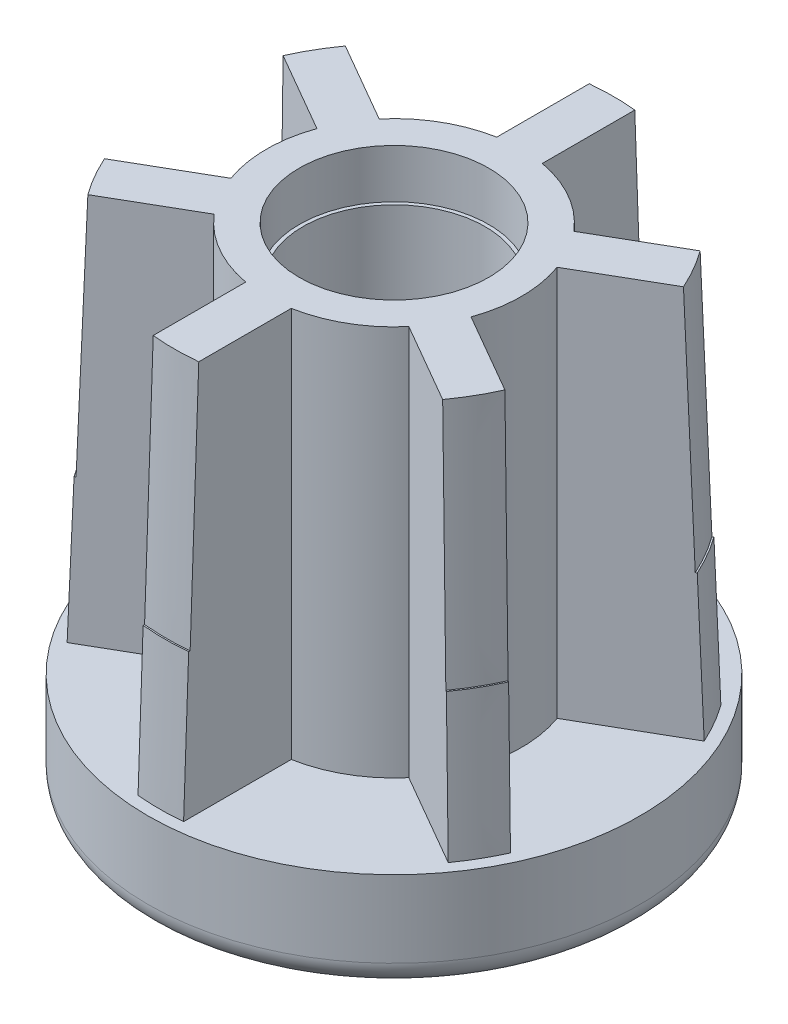
SolidWorks part; units mm, degrees
ref_plane "Front Plane" through (0, 0, 0) normal (0, 0, 1) x (1, 0, 0)
ref_plane "Top Plane" through (0, 0, 0) normal (0, 1, 0) x (1, 0, 0)
ref_plane "Right Plane" through (0, 0, 0) normal (1, 0, 0) x (0, 0, -1)
sketch "Sketch1" plane through (0, 0, 0) normal (1, 0, 0) x (0, 0, -1)
  line L0 (0, 21.4312) -> (0, -21.4312) construction
  line L1 (0, -21.4312) -> (21.4313, -21.4313)
  line L2 (21.4313, -21.4313) -> (21.4313, -12.6048)
  line L3 (21.4313, -12.6048) -> (0, -12.6048)
  line L4 (7.9375, -21.4313) -> (7.9375, 0.7937)
  line L5 (7.9375, 0.7937) -> (0, 0.7937)
  line L6 (9.525, -21.4313) -> (9.525, 0.7937)
  line L7 (9.525, 0.7937) -> (7.9375, 0.7937)
  line L8 (11.1125, -12.6048) -> (11.1125, 21.4312)
  line L9 (11.1125, 21.4312) -> (0, 21.4312)
  line L10 (19.8438, -12.6048) -> (19.8438, 21.4313)
  line L11 (19.8438, 21.4313) -> (11.1125, 21.4312)
  line L12 (19.8438, -12.6048) -> (19.2496, 21.4313)
  line L13 (9.525, 0.7937) -> (11.1125, 0.7937) construction
  line L14 (8.1875, -21.2869) -> (6.1877, -22.4415) construction
  line L15 (6.1877, -22.4415) -> (8.1875, -23.596) construction
  line L16 (8.1875, -23.596) -> (8.1875, -21.2869) construction
  line L17 (8.0625, -21.3591) -> (8.0625, -23.5239)
  line L18 (8.0625, -23.5239) -> (6.4377, -22.5858)
  line L19 (6.4377, -22.5858) -> (6.4377, -22.2972)
  line L20 (6.4377, -22.2972) -> (8.0625, -21.3591)
  line L21 (6.4377, -22.4415) -> (6.1877, -22.4415) construction
  line L22 (7.9375, -21.4313) -> (7.9375, -23.4517) construction
  line L23 (8.1875, -22.4415) -> (7.9375, -22.4415) construction
  line L24 (-7.9375, -21.4313) -> (-7.9375, 0.7937)
  point P2 (0, 0)
  point P16 (10.3188, 0.7937)
  point P31 (8.0625, -22.4415)
  point P33 (19.8438, -12.6048)
  point P35 (-7.9375, -10.3188)
  point P36 (7.9375, -21.4313)
  point P37 (7.9375, -10.3188)
  dimension "Base Diameter" = 42.8625
  dimension "Thread Diameter" = 15.875
  dimension "Thread Depth" = 22.225
  dimension "D1" = 19.05
  dimension "D4" = 22.225
  dimension "Insert Depth" = 34.036
  dimension "Overall Height" = 42.8625
  dimension "For Leg ID" = 39.6875
  dimension "D2" = 1
  dimension "Pitch" = 2.3091
  dimension "D5" = 0.2886
sketch "Sketch2" plane through (0, 0, 0) normal (0, 1, 0) x (1, 0, 0)
  line L0 (-1.9844, 19.7443) -> (1.9844, 19.7443)
  line L1 (-1.9844, 19.7443) -> (-1.9844, 10.9339)
  line L2 (-1.9844, 10.9339) -> (1.9844, 10.9339)
  line L3 (1.9844, 10.9339) -> (1.9844, 19.7443)
  circle A0 centre (0, 0) radius 19.8438
  circle A1 centre (0, 0) radius 11.1125
  dimension "D1" = 3.9688
sketch "Sketch8" plane through (0, 0, 0) normal (1, 0, 0) x (0, 0, -1)
  line L0 (11.1125, -12.6048) -> (11.1125, 21.4312)
  line L1 (11.1125, 21.4312) -> (7.9375, 21.4312)
  line L2 (11.1125, 21.4312) -> (0, 21.4312) construction
  line L3 (7.9375, 21.4312) -> (7.9375, 0.7937)
  line L4 (7.9375, 0.7937) -> (9.525, 0.7937)
  line L9 (0, 21.4312) -> (0, -12.6048) construction
  line L10 (9.525, 0.7937) -> (9.525, -21.4313)
  line L11 (9.525, -21.4313) -> (21.4313, -21.4313)
  line L12 (21.4313, -21.4313) -> (21.4313, -12.6048)
  line L13 (21.4313, -12.6048) -> (11.1125, -12.6048)
revolve "Revolve2" add sketch "Sketch8" angle 360 about L9
sketch "Sketch9" plane through (-13.335, -12.6047, 0) normal (0, 1, 0) x (0, 0, -1)
  line L4 (10.9339, -11.3506) -> (10.9339, -15.3194)
  line L7 (10.9339, -11.3506) -> (21.3392, -11.3506)
  line L8 (10.9339, -15.3194) -> (21.3392, -15.3194)
  circle A0 centre (0, -13.335) radius 21.4313 construction
  arc A1 (21.3392, -15.3194) -> (21.3392, -11.3506) centre (0, -13.335) ccw
extrude "Boss-Extrude3" add sketch "Sketch9" along normal up to vertex (34.036 mm away) up to point (0, 21.4312, 0)
pattern_circular "CirPattern2" count 6 over 360 about axis through (0, -21.4312, 0) along (0, 1, 0) of "Boss-Extrude3"
sketch "Sketch15" plane through (0, 0, 0) normal (1, 0, 0) x (0, 0, -1)
  line L0 (19.8438, -12.6048) -> (21.4313, -12.6048) construction
  line L1 (20.411, -12.6048) -> (19.9708, 0)
  line L2 (19.9708, 0) -> (19.8438, 0)
  line L3 (7.9375, 21.4312) -> (-7.9375, 21.4312) construction
  line L4 (19.8438, 0) -> (19.0954, 21.4312)
  line L5 (19.0954, 21.4312) -> (21.4313, 21.4312)
  line L6 (21.4313, 21.4312) -> (21.4313, -12.6048)
  line L7 (21.4313, -12.6048) -> (20.411, -12.6048)
  line L8 (7.9375, 21.4312) -> (8.255, 21.4312)
  line L9 (7.9375, 21.4312) -> (7.9375, 17.1767)
  line L10 (7.9375, 17.1767) -> (8.255, 17.1767)
  line L11 (8.255, 21.4312) -> (8.255, 17.1767)
  dimension "D1" = 2
  dimension "D2" = 0.127
  dimension "D3" = 0.3175
  dimension "D4" = 4.2545
revolve "Cut-Revolve1" cut sketch "Sketch15" angle 360 about L0
sketch "Sketch10" plane through (0, 0, 0) normal (1, 0, 0) x (0, 0, -1)
  line L0 (0, 0.7937) -> (0, -21.4312) construction
  line L2 (9.525, 0.7937) -> (7.9375, 0.7937)
  line L3 (9.525, 0.7937) -> (9.525, -21.4313)
  line L4 (9.525, -21.4313) -> (7.9375, -21.4313)
  line L5 (7.9375, 0.7937) -> (7.9375, -21.4313)
revolve "Revolve3" add sketch "Sketch10" angle 360 about L0
sketch "Sketch11" plane through (0, -21.4313, 0) normal (0, -1, 0) x (1, 0, 0)
  circle A0 centre (0, 0) radius 7.9375 construction
  circle A1 centre (0, 0) radius 7.9375
fillet "Fillet2" radius 2.1431 1 edges at (0, -21.4312, 21.4312)
curve "Helix/Spiral1" pitch 2.3091 height 24.5341 radius 7.9375 centre (0, -21.4313, 0) axis (0, 1, 0) start towards (0, 0, -1)
sketch "Sketch12" plane through (0, 0, 0) normal (1, 0, 0) x (0, 0, -1)
  line L0 (8.0625, -21.3591) -> (8.0625, -23.5239) construction
  line L1 (6.4377, -22.2972) -> (8.0625, -21.3591) construction
  line L2 (6.4377, -22.5858) -> (6.4377, -22.2972) construction
  line L3 (8.0625, -23.5239) -> (6.4377, -22.5858) construction
  line L4 (8.0625, -21.3591) -> (8.0625, -23.5239)
  line L5 (6.4377, -22.2972) -> (8.0625, -21.3591)
  line L6 (6.4377, -22.5858) -> (6.4377, -22.2972)
  line L7 (8.0625, -23.5239) -> (6.4377, -22.5858)
sweep "Sweep1" add profiles "Sketch12" path "Helix/Spiral1"
sketch "Sketch13" plane through (0, -21.4313, 0) normal (0, -1, 0) x (1, 0, 0)
  circle A0 centre (0, 0) radius 8.1875
extrude "Cut-Extrude1" cut sketch "Sketch13" against normal up to vertex (22.225 mm away) draft 45 and the other way through all up to point (0, 0.7937, 0)
sketch "Sketch14" plane through (0, 0.7937, 0) normal (0, 1, 0) x (1, 0, 0)
  circle A1 centre (0, 0) radius 8.1875
  circle A2 centre (0, 0) radius 8.1875
  dimension "D1" = 0
extrude "Cut-Extrude2" cut sketch "Sketch14" against normal up to vertex (22.225 mm away) draft 45 and the other way through all up to point (0, -21.4312, 0)
equation "\"D1@Sketch1\"=\"Thread Diameter@Sketch1\"*1.2"
equation "\"D1@Sketch2\" = \"For Leg ID@Sketch1\" * 0.1"
equation "\"D4@Sketch1\"=\"Thread Diameter@Sketch1\"*1.4"
equation "\"D5@Sketch1\" = \"Pitch@Sketch1\" / 8"
equation "\"D4@Helix/Spiral1\"=\"Pitch@Sketch1\""
equation "\"D3@Helix/Spiral1\"=\"Pitch@Sketch1\"+\"Thread Depth@Sketch1\""
equation "\"D1@Fillet2\"=0.05*\"Base Diameter@Sketch1\""
equation "\"D4@Sketch15\"=\"Insert Depth@Sketch1\"/8"
